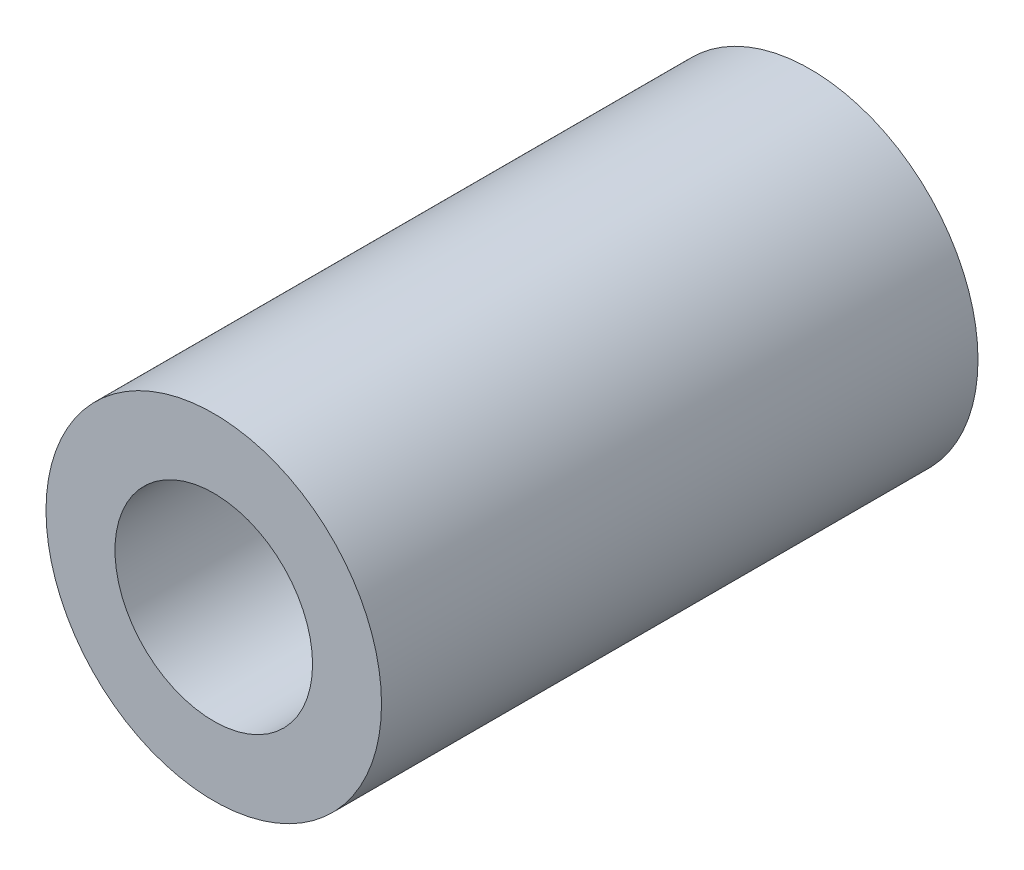
SolidWorks part; units mm, degrees
ref_plane "Front Plane" through (0, 0, 0) normal (0, 0, 1) x (1, 0, 0)
ref_plane "Top Plane" through (0, 0, 0) normal (0, 1, 0) x (1, 0, 0)
ref_plane "Right Plane" through (0, 0, 0) normal (1, 0, 0) x (0, 0, -1)
sketch "Cross Section Sketch" plane through (0, 0, 0) normal (0, 0, 1) x (1, 0, 0)
  circle A0 centre (0, 0) radius 4.5
  circle A1 centre (0, 0) radius 2.65
  dimension "OD" = 9
  dimension "ID" = 5.3
extrude "Extrude Length" add sketch "Cross Section Sketch" along normal mid plane 16
